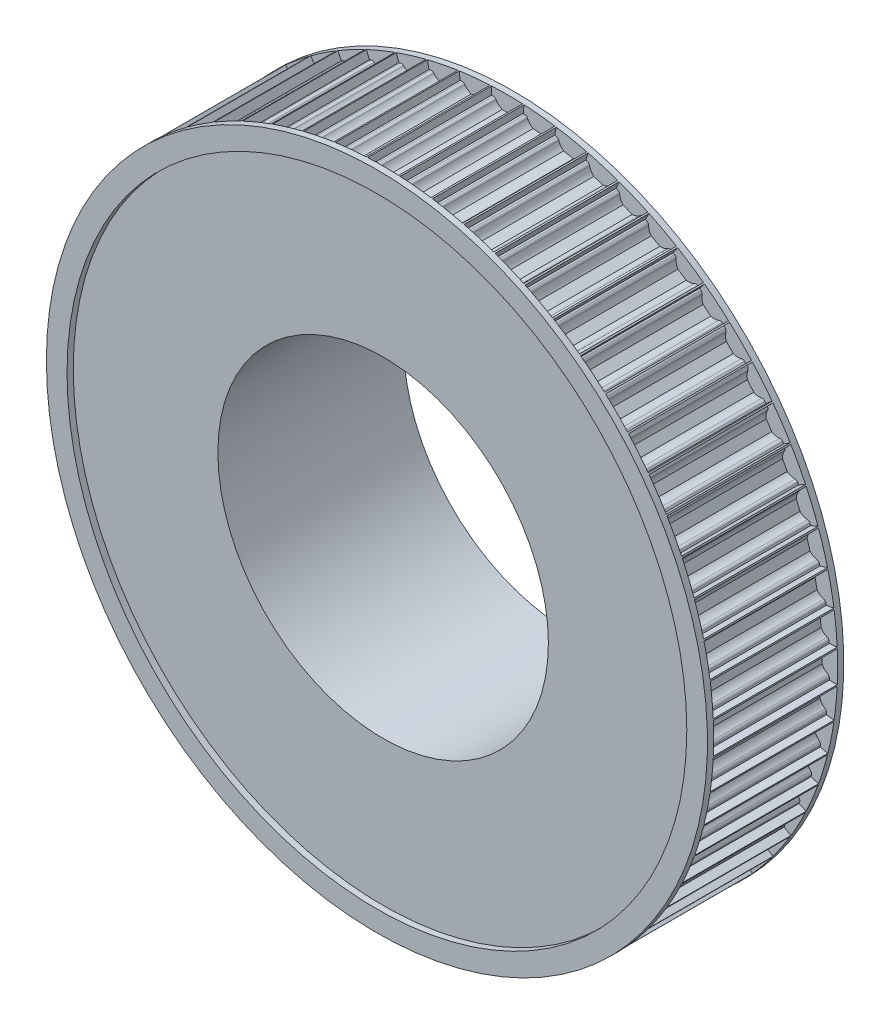
SolidWorks part; units mm, degrees
ref_plane "Front Plane" through (0, 0, 0) normal (0, 0, 1) x (1, 0, 0)
ref_plane "Top Plane" through (0, 0, 0) normal (0, 1, 0) x (1, 0, 0)
ref_plane "Right Plane" through (0, 0, 0) normal (1, 0, 0) x (0, 0, -1)
ref_axis "Axis1" through (0, 0, -88.99) along (0, 0, 1)
sketch "Sketch1" plane through (0, 0, 0) normal (1, 0, 0) x (0, 0, -1)
  line L0 (0, 40) -> (0, 80)
  line L1 (0, 80) -> (30, 80)
  line L2 (30, 80) -> (30, 55.5)
  line L3 (30, 55.5) -> (45, 55.5)
  line L4 (45, 55.5) -> (45, 40)
  line L5 (45, 40) -> (0, 40)
  line L6 (88.99, 0) -> (-88.99, 0) construction
  dimension "D1" = 40
  dimension "D2" = 30
  dimension "D3" = 15
  dimension "D4" = 15.5
  dimension "D5" = 40
revolve "Revolve1" add sketch "Sketch1" angle 360 about axis through (0, 0, -88.99) along (0, 0, 1)
sketch "Sketch2" plane through (0, 0, 0) normal (0, 0, 1) x (1, 0, 0)
  line L0 (3.3166, 78) -> (3.75, 78)
  line L1 (-3.75, 80) -> (3.75, 80)
  line L2 (-3.75, 80) -> (-3.75, 78)
  line L3 (-3.75, 78) -> (-3.3166, 78)
  line L4 (3.75, 80) -> (3.75, 78)
  line L5 (-3.75, 80) -> (3.75, 78) construction
  line L6 (-3.75, 78) -> (3.75, 80) construction
  line L7 (-1.199, 76.25) -> (1.199, 76.25)
  arc A0 (-2.6533, 77.6) -> (-1.199, 76.25) centre (0, 79) ccw
  arc A1 (3.3166, 78) -> (2.6533, 77.6) centre (3.3166, 77.25) ccw
  arc A2 (-2.6533, 77.6) -> (-3.3166, 78) centre (-3.3166, 77.25) ccw
  arc A3 (1.199, 76.25) -> (2.6533, 77.6) centre (0, 79) ccw
  point P7 (0, 79)
  point P11 (2.8284, 78)
  dimension "D3" = 3
  dimension "D5" = 0.75
  dimension "D1" = 2
  dimension "D2" = 7.5
  dimension "D4" = 79
  dimension "D6" = 2.75
extrude "Cut-Extrude1" cut sketch "Sketch2" against normal through all
pattern_circular "CirPattern1" count 64 over 360 about axis through (0, 0, -88.99) along (0, 0, 1) of "Cut-Extrude1"
sketch "Sketch3" plane through (0, 0, 0) normal (1, 0, 0) x (0, 0, -1)
  line L1 (-1.5, 80) -> (0, 80)
  line L2 (-1.5, 80) -> (-1.5, 75)
  line L3 (-1.5, 75) -> (0, 75)
  line L4 (0, 80) -> (0, 75)
  line L5 (-1.5, 80) -> (0, 75) construction
  line L6 (-1.5, 75) -> (0, 80) construction
  line L7 (0, 80) -> (-1.4489, 79.6118) construction
  line L8 (0, 80) -> (-0.6431, 82.4)
  line L9 (-1.4489, 79.6118) -> (-2.092, 82.0118)
  line L10 (-0.6431, 82.4) -> (-2.092, 82.0118)
  line L11 (0, 80) -> (-2.092, 82.0118) construction
  line L12 (-1.4489, 79.6118) -> (-0.6431, 82.4) construction
  line L13 (88.99, 0) -> (-88.99, 0) construction
  line L14 (15, 20.9869) -> (15, 38.8724) construction
  line L15 (30, 20.9869) -> (0, 20.9869) construction
  line L16 (31.4489, 79.6118) -> (30.6431, 82.4) construction
  line L17 (30, 80) -> (32.092, 82.0118) construction
  line L18 (30, 80) -> (31.4489, 79.6118) construction
  line L19 (31.5, 75) -> (30, 80) construction
  line L20 (31.5, 80) -> (30, 75) construction
  line L21 (30.6431, 82.4) -> (32.092, 82.0118)
  line L22 (31.4489, 79.6118) -> (32.092, 82.0118)
  line L23 (30, 80) -> (30.6431, 82.4)
  line L24 (30, 80) -> (30, 75)
  line L25 (31.5, 75) -> (30, 75)
  line L26 (31.5, 80) -> (31.5, 75)
  line L27 (31.5, 80) -> (30, 80)
  line L28 (0, -1.199) -> (0, -2.6533) construction
  point P4 (0, 0)
  point P5 (0, 0)
  point P12 (-1.046, 81.0059)
  point P24 (31.046, 81.0059)
  point P25 (30.28, 25)
  point P26 (-11.0306, 29.2551)
  point P27 (-7.1042, 27.7521)
  point P28 (0, 0)
  point P30 (-17.3736, -13.3092)
  dimension "D1" = 1.5
  dimension "D2" = 5
  dimension "D3" = 1.5
  dimension "D4" = 165
  dimension "D5" = 2.4
  dimension "D6" = 75
revolve "Revolve2" add sketch "Sketch3" angle 360 about axis through (0, 0, -88.99) along (0, 0, 1)
